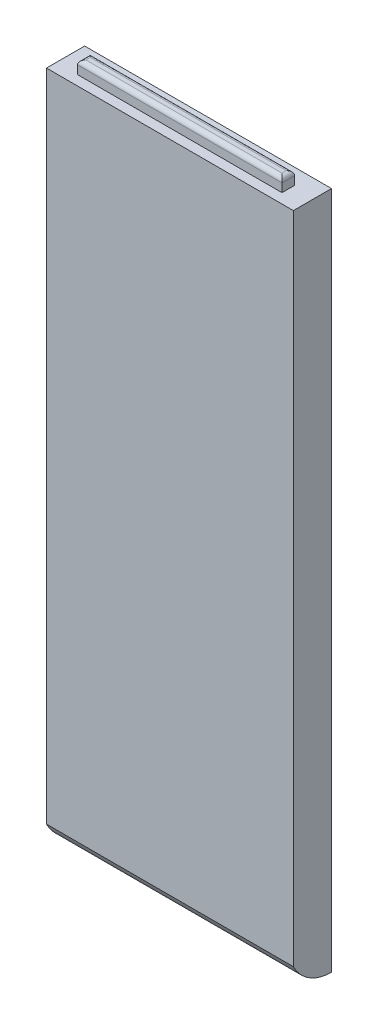
SolidWorks part; units mm, degrees
ref_plane "Front Plane" through (0, 0, 0) normal (0, 0, 1) x (1, 0, 0)
ref_plane "Top Plane" through (0, 0, 0) normal (0, 1, 0) x (1, 0, 0)
ref_plane "Right Plane" through (0, 0, 0) normal (1, 0, 0) x (0, 0, -1)
sketch "Sketch1" plane through (0, 0, 0) normal (0, 0, 1) x (1, 0, 0)
  line L1 (0, 0) -> (58.2, 0)
  line L2 (0, 0) -> (0, 160)
  line L3 (0, 160) -> (58.2, 160)
  line L4 (58.2, 0) -> (58.2, 160)
  dimension "D1" = 160
  dimension "D2" = 58.2
extrude "Boss-Extrude2" add sketch "Sketch1" along normal blind 10
fillet "Fillet2" radius 10 1 edges at (29.1, 0, 10)
sketch "Sketch2" plane through (0, 0, 0) normal (0, 0, -1) x (-1, 0, 0)
  line L0 (-58.2, 0) -> (-58.2, 160) construction
  line L1 (-53.2, 3.65) -> (-5, 3.65)
  line L2 (-53.2, 3.65) -> (-53.2, 1.35)
  line L3 (-53.2, 1.35) -> (-5, 1.35)
  line L4 (-5, 3.65) -> (-5, 1.35)
  line L5 (0, 160) -> (0, 0) construction
  line L6 (0, 0) -> (-58.2, 0) construction
  dimension "D1" = 5
  dimension "D2" = 5
  dimension "D3" = 1.35
  dimension "D4" = 2.3
extrude "Boss-Extrude3" add sketch "Sketch2" along normal blind 3
fillet "Fillet3" radius 1 4 edges at (5, 2.5, -3) (29.1, 1.35, -3) (53.2, 2.5, -3) (29.1, 3.65, -3)
sketch "Sketch4" plane through (0, 160, 0) normal (0, 1, 0) x (1, 0, 0)
  line L0 (0, -10) -> (0, 0) construction
  line L1 (5, -3.6809) -> (53.2, -3.6809)
  line L2 (5, -3.6809) -> (5, -6.6809)
  line L3 (5, -6.6809) -> (53.2, -6.6809)
  line L4 (53.2, -3.6809) -> (53.2, -6.6809)
  line L5 (58.2, -10) -> (58.2, 0) construction
  dimension "D1" = 3
  dimension "D2" = 5
  dimension "D3" = 5
extrude "Boss-Extrude4" add sketch "Sketch4" along normal blind 3
fillet "Fillet4" radius 1 4 edges at (53.2, 163, 5.1809) (29.1, 163, 3.6809) (5, 163, 5.1809) (29.1, 163, 6.6809)
sketch "Sketch5" plane through (0, 0, 10) normal (0, 0, 1) x (1, 0, 0)
  line L1 (0, 160) -> (58.2, 160)
  line L2 (0, 160) -> (0, 0)
  line L3 (0, 0) -> (58.2, 0)
  line L4 (58.2, 160) -> (58.2, 0)
extrude "Cut-Extrude1" cut sketch "Sketch5" against normal blind 1
